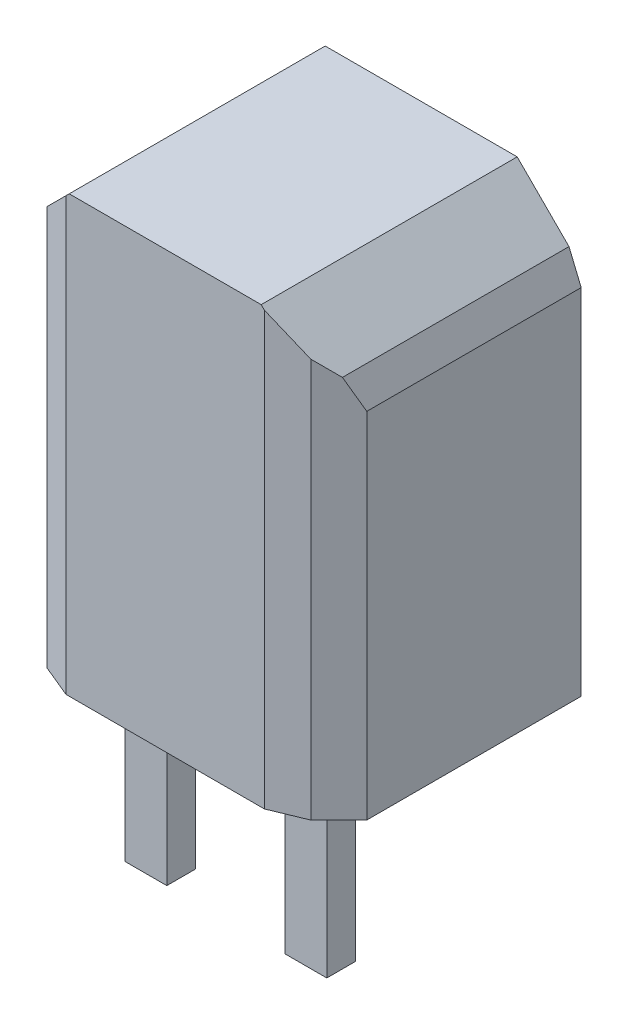
SolidWorks part; units mm, degrees
ref_plane "Ön Düzlem" through (0, 0, 0) normal (0, 0, 1) x (1, 0, 0)
ref_plane "Üst Düzlem" through (0, 0, 0) normal (0, 1, 0) x (1, 0, 0)
ref_plane "Sağ Düzlem" through (0, 0, 0) normal (1, 0, 0) x (0, 0, -1)
sketch "Çizim1" plane through (0, 0, 0) normal (0, 0, 1) x (1, 0, 0)
  line L0 (0, 0) -> (0, 6.8) construction
  line L1 (0, 0) -> (5, 0)
  line L2 (1, 6.8) -> (4, 6.8)
  line L3 (5, 5.8) -> (5, 0)
  line L4 (4, 6.8) -> (5, 5.8)
  line L5 (0, 0) -> (0, 5.8)
  line L6 (0, 5.8) -> (1, 6.8)
  point P3 (5, 6.8)
  dimension "D1" = 6.8
  dimension "D2" = 5
extrude "Yükseklik-Ekstrüzyon1" add sketch "Çizim1" along normal blind 4
chamfer "Pah2" distance 0.65 angle 45 2 edges at (5, 2.9, 4) (0, 2.9, 4)
fillet "Pah3" radius 0.65 1 edges at (0, 5.8, 1.675)
fillet "Pah4" radius 0.65 1 edges at (5, 5.8, 1.675)
chamfer "Pah7" distance 0.3 1 edges at (0.65, 3.225, 4)
chamfer "Pah8" distance 0.3 1 edges at (4.35, 3.225, 4)
sketch "Çizim2" plane through (0, 0, 0) normal (0, -1, 0) x (1, 0, 0)
  line L0 (2.5, 1.4) -> (2.5, 4.378) construction
  line L1 (0, 3.35) -> (0, 0) construction
  line L2 (0.925, 3.05) -> (1.575, 3.05)
  line L3 (0.925, 3.05) -> (0.925, 2.6)
  line L4 (0.925, 2.6) -> (1.575, 2.6)
  line L5 (1.575, 3.05) -> (1.575, 2.6)
  line L6 (0.925, 3.05) -> (1.575, 2.6) construction
  line L7 (0.925, 2.6) -> (1.575, 3.05) construction
  line L9 (0.95, 4) -> (4.05, 4) construction
  line L10 (0, 0) -> (5, 0) construction
  line L11 (3.425, 3.05) -> (3.425, 2.6)
  line L12 (4.075, 2.6) -> (3.425, 2.6)
  line L13 (4.075, 3.05) -> (4.075, 2.6)
  line L14 (4.075, 3.05) -> (3.425, 3.05)
  point P2 (1.25, 2.825)
  dimension "D1" = 1.25
  dimension "D2" = 2.5
  dimension "D3" = 0.45
  dimension "D4" = 0.65
  dimension "D5" = 1.4
  dimension "D6" = 1.4
extrude "Yükseklik-Ekstrüzyon2" add sketch "Çizim2" along normal blind 2.75
